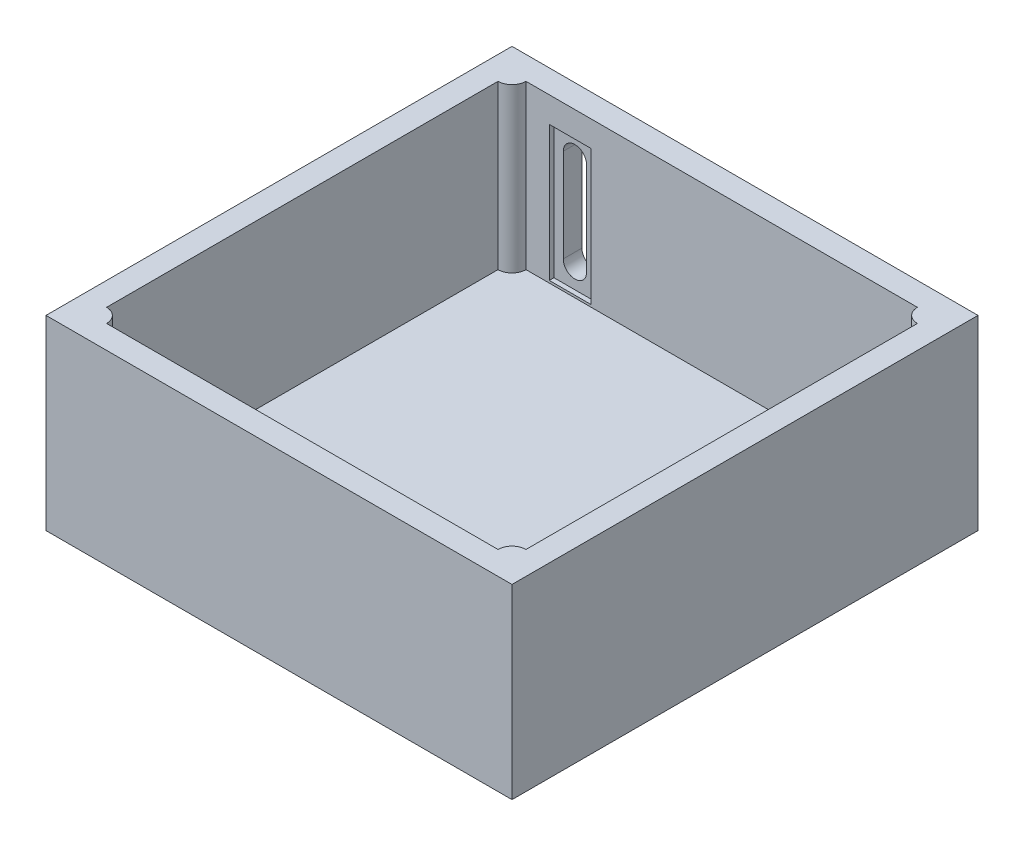
SolidWorks part; units mm, degrees
ref_plane "Front Plane" through (0, 0, 0) normal (0, 0, 1) x (1, 0, 0)
ref_plane "Top Plane" through (0, 0, 0) normal (0, 1, 0) x (1, 0, 0)
ref_plane "Right Plane" through (0, 0, 0) normal (1, 0, 0) x (0, 0, -1)
sketch "Sketch1" plane through (0, 0, 0) normal (0, 1, 0) x (1, 0, 0)
  line L1 (100, -100) -> (-100, -100)
  line L2 (100, -100) -> (100, 100)
  line L3 (100, 100) -> (-100, 100)
  line L4 (-100, -100) -> (-100, 100)
  line L5 (100, -100) -> (-100, 100) construction
  line L6 (100, 100) -> (-100, -100) construction
  point P0 (0, 0)
  dimension "D1" = 200
  dimension "D2" = 200
extrude "Boss-Extrude1" add sketch "Sketch1" along normal blind 100
chamfer "Chamfer1" distance 20 angle 45 4 edges at (100, 0, 0) (0, 0, -100) (-100, 0, 0) (0, 0, 100)
sketch "Sketch2" plane through (0, 100, 0) normal (0, 1, 0) x (1, 0, 0)
  line L0 (0, 0) -> (-179.5549, 0) construction
  line L1 (0, 0) -> (0, 117.1127) construction
  line L2 (-100, 100) -> (-100, -100) construction
  line L3 (100, 100) -> (-100, 100) construction
  line L4 (-84, 90) -> (84, 90)
  line L5 (90, 84) -> (90, -84)
  line L6 (84, -90) -> (-84, -90)
  line L7 (-90, 87) -> (-90, -84)
  circle A0 centre (-90, 90) radius 3
  circle A1 centre (90, 90) radius 3
  circle A2 centre (90, -90) radius 3
  circle A3 centre (-90, -90) radius 3
  circle A4 centre (-90, 90) radius 6
  circle A5 centre (90, 90) radius 6
  circle A6 centre (90, -90) radius 6
  circle A7 centre (-90, -90) radius 6
  dimension "D1" = 6
  dimension "D2" = 10
  dimension "D3" = 10
  dimension "D4" = 3
extrude "Cut-Extrude3" cut sketch "Sketch2" against normal blind 70 contours L7 A7 L6 A6 L5 A5 L4 A4 region at (0, 100, 0)
sketch "Sketch6" plane through (0, 100, 0) normal (0, 1, 0) x (1, 0, 0)
extrude "Cut-Extrude4" cut sketch "Sketch2<7>" against normal through all from offset 70 contours A2 | A3 | A0 | A1 region at (90, 100, 90) offset against normal yes
sketch "Sketch2<7>" plane through (0, 100, 0) normal (0, 1, 0) x (1, 0, 0) same geometry as "Sketch2"
sketch "Sketch7" plane through (0, 0, -100) normal (0, 0, -1) x (-1, 0, 0)
  line L0 (65, 80) -> (65, 40) construction
  line L1 (70, 80) -> (70, 40)
  line L2 (60, 80) -> (60, 40)
  line L3 (100, 100) -> (100, 20) construction
  line L4 (100, 60) -> (60, 60) construction
  arc A0 (70, 80) -> (60, 80) centre (65, 80) ccw
  arc A1 (60, 40) -> (70, 40) centre (65, 40) ccw
  point P2 (65, 60)
  dimension "D2" = 5
  dimension "D3" = 40
  dimension "D1" = 30
extrude "Cut-Extrude7" cut sketch "Sketch7" against normal up to surface (10 mm away) up to face at (0, 65, -90)
sketch "Sketch9" plane through (0, 0, -90) normal (0, 0, 1) x (1, 0, 0)
  line L0 (-60, 60) -> (-56, 60) construction
  line L1 (-74, 89) -> (-56, 89)
  line L2 (-74, 89) -> (-74, 31)
  line L3 (-74, 31) -> (-56, 31)
  line L4 (-56, 89) -> (-56, 31)
  line L5 (-60, 80) -> (-60, 40) construction
  line L6 (-65, 35) -> (-65, 31) construction
  arc A0 (-70, 40) -> (-60, 40) centre (-65, 40) ccw construction
  dimension "D1" = 4
  dimension "D2" = 4
extrude "Cut-Extrude8" cut sketch "Sketch9" against normal blind 2
extrude "Cut-Extrude9" cut sketch "Sketch2<8>" against normal through all from offset 80 contours A5 A1 | A6 A2 | A7 A3 | A4 A0 region at (-85.8774, 100, -85.8774) region at (90, 100, -95.8303) region at (-85.8774, 100, 85.8774) region at (94.1226, 100, 85.8774) offset against normal yes
sketch "Sketch2<8>" plane through (0, 100, 0) normal (0, 1, 0) x (1, 0, 0) same geometry as "Sketch2"
